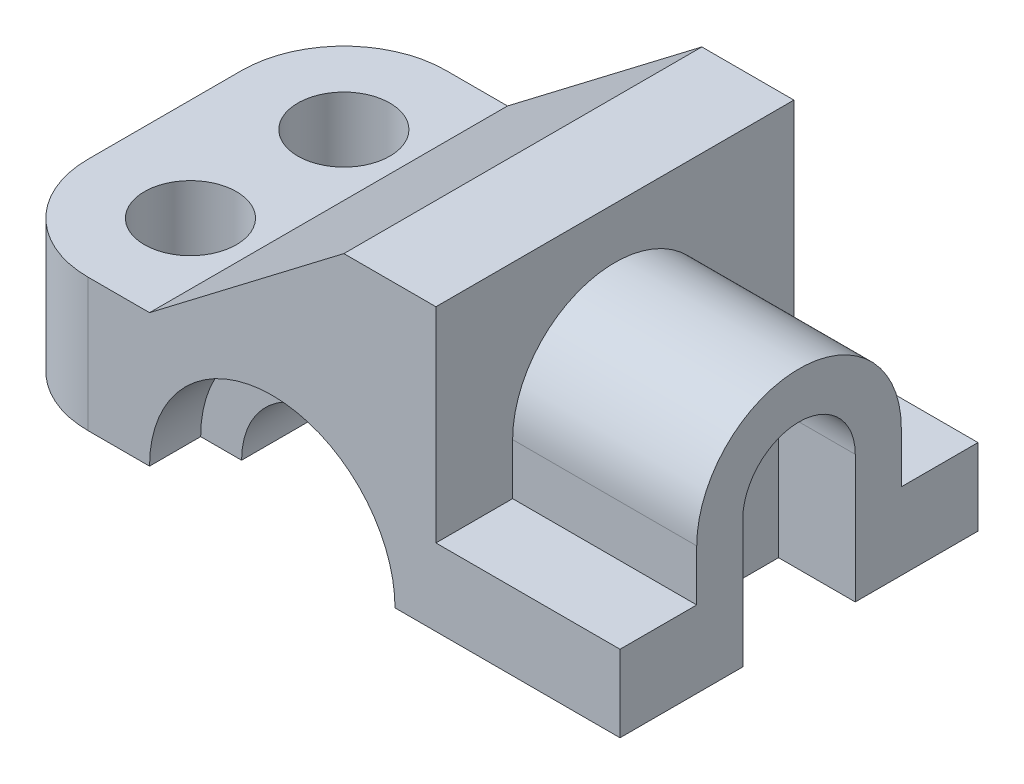
SolidWorks part; units mm, degrees
ref_plane "前基準面" through (0, 0, 0) normal (0, 0, 1) x (1, 0, 0)
ref_plane "上基準面" through (0, 0, 0) normal (0, 1, 0) x (1, 0, 0)
ref_plane "右基準面" through (0, 0, 0) normal (1, 0, 0) x (0, 0, -1)
sketch "草圖3" plane through (0, 0, 0) normal (0, 0, 1) x (1, 0, 0)
  line L0 (0, 0) -> (0, 26)
  line L1 (0, 26) -> (32, 26)
  line L2 (32, 26) -> (70, 55)
  line L3 (70, 55) -> (88, 55)
  line L4 (88, 55) -> (88, 15)
  line L5 (88, 15) -> (124, 15)
  line L6 (124, 15) -> (124, 0)
  line L7 (124, 0) -> (30.6974, 0)
  line L8 (30.6974, 0) -> (0, 0)
  dimension "D1" = 124
  dimension "D2" = 55
  dimension "D3" = 18
  dimension "D4" = 38
  dimension "D5" = 32
  dimension "D6" = 26
  dimension "D7" = 15
extrude "填料-伸長1" add sketch "草圖3" against normal blind 70
fillet "圓角1" radius 20 2 edges at (0, 13, -70) (0, 13, 0)
sketch "草圖4" plane through (0, 26, 0) normal (0, 1, 0) x (1, 0, 0)
  line L0 (0, 35) -> (47.0394, 35) construction
  line L1 (0, 50) -> (0, 20) construction
  circle A0 centre (20, 20) radius 9
  circle A1 centre (20, 50) radius 9
  dimension "D1" = 18
extrude "除料-伸長1" cut sketch "草圖4" against normal through all
sketch "草圖5" plane through (0, 0, 0) normal (0, 0, 1) x (1, 0, 0)
  line L0 (20, 0) -> (124, 0) construction
  line L1 (32, 0) -> (40, 0)
  line L2 (72, 0) -> (80, 0)
  line L3 (88, 15) -> (88, 55) construction
  arc A0 (80, 0) -> (32, 0) centre (56, 0) ccw
  arc A1 (72, 0) -> (40, 0) centre (56, 0) ccw
  line M3 (20, 0) -> (124, 0)
  dimension "D1" = 24
  dimension "D2" = 16
  dimension "D3" = 32
extrude "除料-伸長2" cut sketch "草圖5" against normal blind 10 contours A1 A0 M3 region at (56, 23.4633, 0)
extrude "除料-伸長3" cut sketch "草圖5<3>" against normal through all contours A1 M3 region at (56, 6.7906, 0)
sketch "草圖5<3>" plane through (0, 0, 0) normal (0, 0, 1) x (1, 0, 0) same geometry as "草圖5"
sketch "草圖6" plane through (0, 0, -70) normal (0, 0, -1) x (-1, 0, 0)
  circle A0 centre (-56, 0) radius 24
  dimension "D1" = 48
extrude "除料-伸長4" cut sketch "草圖6" against normal blind 10
sketch "草圖7" plane through (88, 0, 0) normal (1, 0, 0) x (0, 0, -1)
  line L0 (35, 15) -> (35, 56.9798) construction
  line L1 (70, 15) -> (0, 15) construction
  line L2 (15, 15) -> (15, 25)
  line L3 (70, 15) -> (0, 15) construction
  line L4 (55, 15) -> (55, 25)
  line L5 (70, 0) -> (0, 0) construction
  line L7 (0, 15) -> (0, 55) construction
  line L8 (15, 15) -> (55, 15)
  arc A0 (15, 25) -> (55, 25) centre (35, 25) cw
  line M5 (0, 15) -> (70, 15)
  dimension "D1" = 15
  dimension "D2" = 25
extrude "填料-伸長2" add sketch "草圖7" along normal blind 36 contours L0 L8 L4 A0 | L0 A0 L2 M5 region at (88, 28.2415, -25.9237) region at (88, 28.2415, -44.0763)
sketch "草圖8" plane through (124, 0, 0) normal (1, 0, 0) x (0, 0, -1)
  line L0 (24, 0) -> (24, 25)
  line L1 (70, 0) -> (0, 0) construction
  line L2 (46, 25) -> (46, 0)
  line L3 (46, 0) -> (24, 0)
  line L4 (70, 0) -> (70, 15) construction
  arc A0 (24, 25) -> (46, 25) centre (35, 25) cw
  dimension "D3" = 25
  dimension "D1" = 22
  dimension "D2" = 24
extrude "除料-伸長5" cut sketch "草圖8" against normal blind 15
